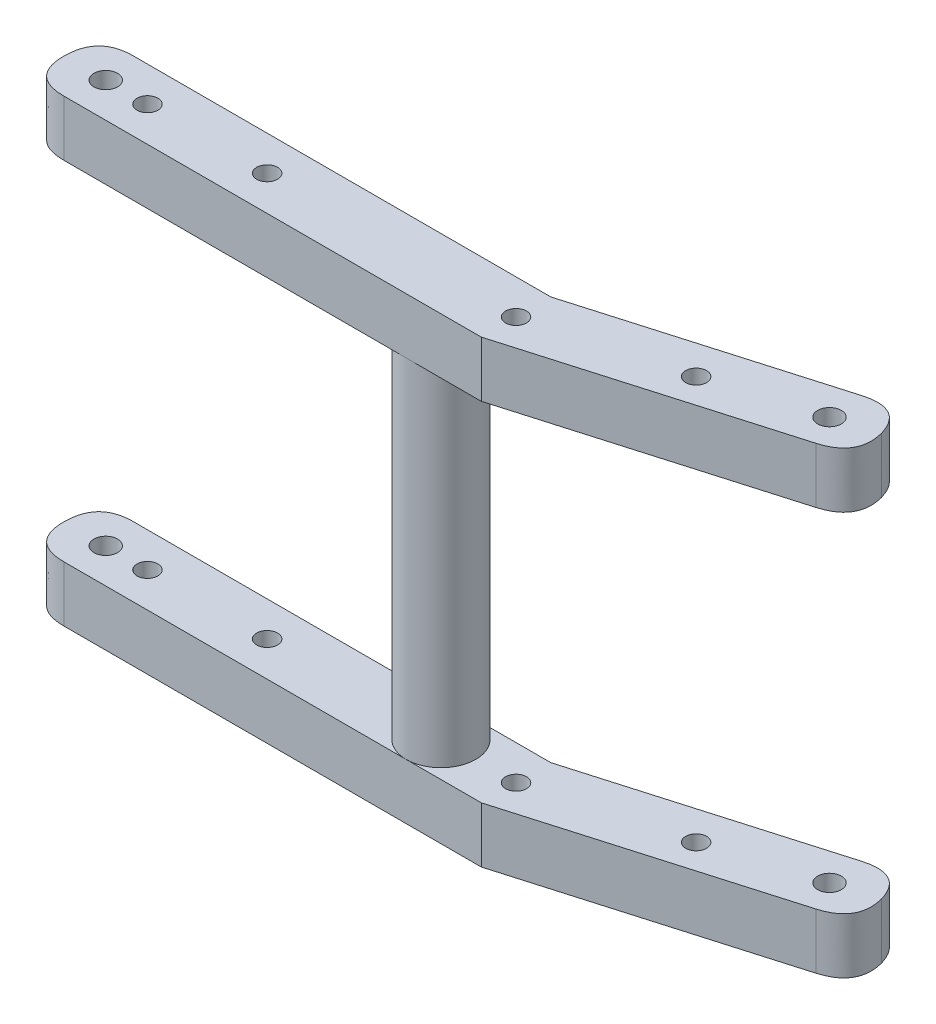
SolidWorks part; units mm, degrees
ref_plane "Front Plane" through (0, 0, 0) normal (0, 0, 1) x (1, 0, 0)
ref_plane "Top Plane" through (0, 0, 0) normal (0, 1, 0) x (1, 0, 0)
ref_plane "Right Plane" through (0, 0, 0) normal (1, 0, 0) x (0, 0, -1)
sketch "Sketch1" plane through (0, 0, 0) normal (0, 1, 0) x (1, 0, 0)
  line L3 (0, -4.2034) -> (0, 5.7966) construction
  line L5 (0, 5.7966) -> (-65, 5.7966)
  line L6 (0, -4.2034) -> (-65, -4.2034)
  line L7 (-65, -4.2034) -> (-65, 5.7966)
  line L8 (0, 5.7966) -> (39.5, 17.2764)
  line L9 (0, -4.2034) -> (42, 8.003)
  line L10 (42, 8.003) -> (39.5, 17.2764)
  dimension "D1" = 10
  dimension "D2" = 39.5
  dimension "D3" = 42
  dimension "D4" = 65
extrude "Boss-Extrude1" add sketch "Sketch1" along normal blind 8
sketch "Sketch2" plane through (0, 8, 0) normal (0, 1, 0) x (1, 0, 0)
  line L0 (-65, 0.7966) -> (-6.7929, 0.7966) construction
  line L1 (-65, 5.7966) -> (-65, -4.2034) construction
  line L2 (0, 5.7966) -> (0, -4.2034) construction
  line L3 (42, 8.003) -> (39.5, 17.2764) construction
  line L4 (40.75, 12.6397) -> (0, 0) construction
  circle A0 centre (-59, 0.7966) radius 1.7
  circle A1 centre (-53, 0.7966) radius 1.5
  circle A2 centre (-35.7929, 0.7966) radius 1.5
  circle A8 centre (20.375, 6.3198) radius 1.5
  circle A9 centre (35.0153, 10.8609) radius 1.7
  circle A10 centre (0, 0.7966) radius 1.5
  dimension "D1" = 3
  dimension "D2" = 3.4
  dimension "D3" = 3
  dimension "D6" = 3
  dimension "D7" = 3
  dimension "D8" = 3.4
  dimension "D15" = 6
  dimension "D16" = 6
  dimension "D9" = 6
extrude "Cut-Extrude1" cut sketch "Sketch2" against normal blind 10
fillet "Fillet1" radius 5 2 edges at (-65, 4, 4.2034) (-65, 4, -5.7966) conic rho 0.5
fillet "Fillet2" radius 5 2 edges at (39.5, 4, -17.2764) (42, 4, -8.003) conic rho 0.5
sketch "Sketch3" plane through (0, 8, 0) normal (0, 1, 0) x (1, 0, 0)
  circle A0 centre (-10.7929, 0.7966) radius 5
  circle A1 centre (-35.7929, 0.7966) radius 1.5 construction
  dimension "D1" = 10
  dimension "D2" = 25
extrude "Boss-Extrude2" add sketch "Sketch3" along normal blind 25
ref_plane "Plane1" through (0, 33, 0) normal (0, 1, 0) x (1, 0, 0)
mirror "Mirror3" about plane through (0, 33, 0) normal (0, 1, 0) of bodies 104
